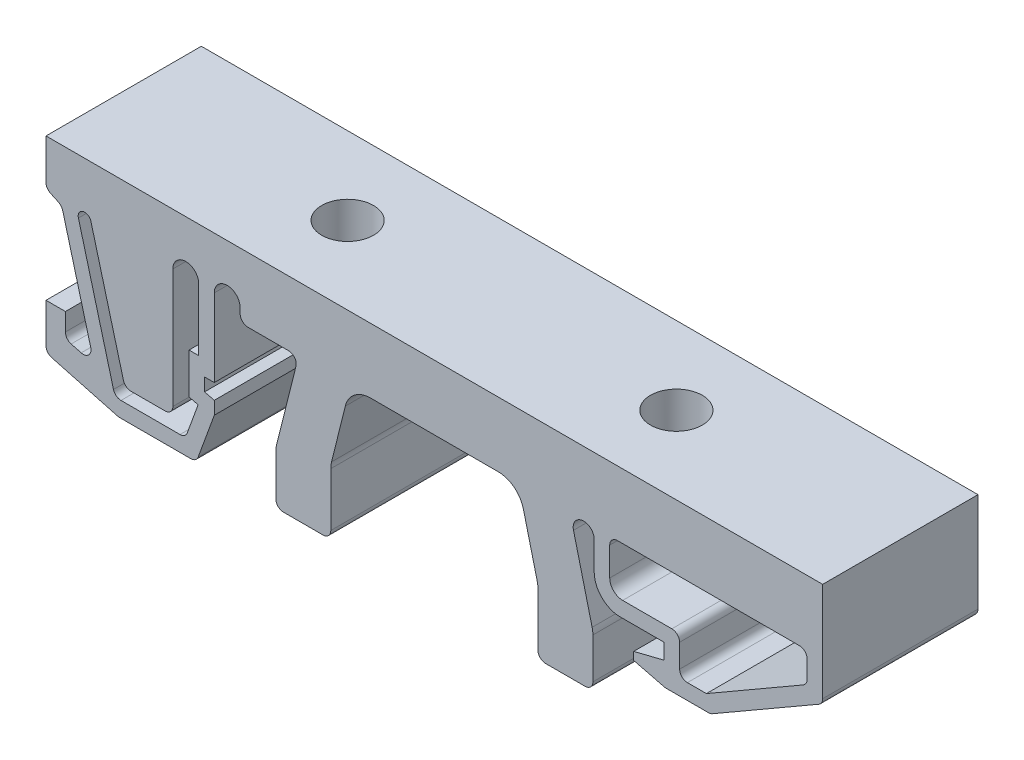
SolidWorks part; units mm, degrees
ref_plane "Front Plane" through (0, 0, 0) normal (0, 0, 1) x (1, 0, 0)
ref_plane "Top Plane" through (0, 0, 0) normal (0, 1, 0) x (1, 0, 0)
ref_plane "Right Plane" through (0, 0, 0) normal (1, 0, 0) x (0, 0, -1)
sketch "Sketch2" plane through (0, 0, 0) normal (0, 0, 1) x (1, 0, 0)
  line L0 (0, 22.5226) -> (0, -8.8845) construction
  line L1 (6.5, 11) -> (-6.5, 11)
  line L2 (-6.5, 11) -> (-8, 4.9838)
  line L3 (-8, 4.9838) -> (-8, 0)
  line L4 (-8, 0) -> (-12.25, 0)
  line L5 (-12.25, 0) -> (-12.25, 3.9811)
  line L6 (-12.25, 3.9811) -> (-10.5, 11)
  line L7 (-10.5, 11) -> (-15, 11)
  line L8 (-15, 11) -> (-15, 13)
  line L9 (-15, 13) -> (-17, 13)
  line L10 (-17, 13) -> (-17, 6)
  line L11 (-17, 6) -> (-17.75, 6)
  line L12 (-17.75, 6) -> (-17.75, 5)
  line L13 (-17.75, 5) -> (-17, 4.813)
  line L14 (-17, 4.813) -> (-17, 3.813)
  line L15 (-17, 3.813) -> (-18.3878, 0)
  line L16 (-18.3878, 0) -> (-24.3878, 0)
  line L17 (-24.3878, 0) -> (-30, 1.5038)
  line L18 (-30, 1.5038) -> (-30, 5.0038)
  line L19 (-30, 5.0038) -> (-28.5, 5.0038)
  line L20 (-28.5, 5.0038) -> (-28.5, 3.1724)
  line L21 (-28.5, 3.1724) -> (-26.2784, 2.5771)
  line L22 (-26.2784, 2.5771) -> (-28.7854, 11.9336)
  line L23 (-28.7854, 11.9336) -> (-30, 12.5)
  line L24 (-30, 12.5) -> (-30, 16)
  line L25 (-30, 16) -> (0, 16)
  line L30 (-8, 0) -> (0, 0) construction
  line L32 (10.5, 11) -> (12.35, 11)
  line L33 (12.25, 3.9811) -> (10.5, 11)
  line L34 (12.25, 0) -> (12.25, 3.9811)
  line L35 (8, 0) -> (12.25, 0)
  line L36 (8, 4.9838) -> (8, 0)
  line L37 (6.5, 11) -> (8, 4.9838)
  line L38 (12.35, 11) -> (12.35, 6)
  line L40 (12.35, 6) -> (17.75, 6)
  line L41 (17.75, 6) -> (17.75, 4.8)
  line L42 (17.75, 4.8) -> (15.4, 4.2141)
  line L43 (15.4, 4.2141) -> (15.4, 3.6083)
  line L44 (15.4, 3.6083) -> (17.8397, 3)
  line L45 (17.8397, 3) -> (21.3397, 3)
  line L46 (21.3397, 3) -> (30, 8)
  line L47 (30, 8) -> (30, 16)
  line L48 (30, 16) -> (0, 16)
  line L49 (-17.75, 6) -> (0, 6) construction
  line L50 (0, 6) -> (17.75, 6) construction
  line L54 (15.4, 3.9112) -> (22.918, 3.9112) construction
  line L56 (-8, 0) -> (8, 0) construction
  point P37 (0, 11)
  dimension "D1" = 5
  dimension "D2" = 16
  dimension "D3" = 104
  dimension "D4" = 16
  dimension "D5" = 13
  dimension "D6" = 24.5
  dimension "D7" = 4
  dimension "D8" = 2
  dimension "D9" = 2
  dimension "D10" = 4.5
  dimension "D11" = 35.5
  dimension "D12" = 7
  dimension "D13" = 1
  dimension "D14" = 1
  dimension "D15" = 20
  dimension "D16" = 6
  dimension "D17" = 15
  dimension "D18" = 1.5
  dimension "D19" = 3.5
  dimension "D20" = 2
  dimension "D21" = 60
  dimension "D22" = 60
  dimension "D23" = 50
  dimension "D24" = 3.5
  dimension "D25" = 2.3
  dimension "D26" = 60
  dimension "D27" = 8
  dimension "D28" = 15.4
  dimension "D29" = 3.5
  dimension "D30" = 1.2
  dimension "D31" = 5.4
  dimension "D32" = 3
extrude "Boss-Extrude1" add sketch "Sketch2" along normal mid plane 12
sketch "Sketch3" plane through (0, 0, 0) normal (0, 0, 1) x (1, 0, 0)
  line L0 (-27.6263, 12.2442) -> (-24.667, 1.2)
  line L1 (-24.667, 1.2) -> (-19.2281, 1.2)
  line L2 (-19.2281, 1.2) -> (-18.2498, 3.8879)
  line L3 (-18.2498, 3.8879) -> (-18.95, 4.0625)
  line L4 (-18.95, 4.0625) -> (-18.95, 7.2)
  line L5 (-18.95, 7.2) -> (-18.2, 7.2)
  line L6 (-18.2, 7.2) -> (-18.2, 13)
  line L7 (-18.2, 13) -> (-20.2, 13)
  line L8 (-20.2, 13) -> (-20.2, 2.2)
  line L9 (-20.2, 2.2) -> (-23.8997, 2.2)
  line L10 (-23.8997, 2.2) -> (-26.6604, 12.503)
  line L11 (-26.6604, 12.503) -> (-27.6263, 12.2442)
  line L12 (13.55, 11) -> (13.55, 7.2)
  line L13 (13.55, 7.2) -> (18.95, 7.2)
  line L14 (18.95, 7.2) -> (18.95, 4.2)
  line L15 (18.95, 4.2) -> (21.0182, 4.2)
  line L16 (21.0182, 4.2) -> (28.8, 8.6928)
  line L17 (28.8, 8.6928) -> (28.8, 11)
  line L18 (28.8, 11) -> (13.55, 11)
  line L19 (-28.7854, 11.9336) -> (-26.2784, 2.5771) construction
  line L20 (-18.3878, 0) -> (-17, 3.813) construction
  line L21 (-24.3878, 0) -> (-18.3878, 0) construction
  line L22 (-17.75, 5) -> (-17.75, 6) construction
  line L23 (-17, 6) -> (-17, 13) construction
  line L26 (-17, 4.813) -> (-17.75, 5) construction
  line L27 (-17.75, 6) -> (-17, 6) construction
  line L28 (-17, 13) -> (-15, 13) construction
  line L29 (12.35, 11) -> (12.35, 6) construction
  line L30 (12.35, 6) -> (17.75, 6) construction
  line L31 (17.75, 6) -> (17.75, 4.8) construction
  line L32 (30, 8) -> (30, 16) construction
  line L33 (21.3397, 3) -> (30, 8) construction
  line L34 (17.8397, 3) -> (21.3397, 3) construction
  line L35 (10.5, 11) -> (12.35, 11) construction
  dimension "D1" = 1.2
  dimension "D2" = 1.2
  dimension "D3" = 1.2
  dimension "D4" = 1.2
  dimension "D5" = 1.2
  dimension "D6" = 2
  dimension "D7" = 1
  dimension "D8" = 1.2
  dimension "D9" = 1.2
  dimension "D10" = 1.2
  dimension "D11" = 1.2
  dimension "D12" = 1.2
  dimension "D13" = 1.2
  dimension "D14" = 1.2
  dimension "D15" = 1.2
  dimension "D16" = 1
extrude "Cut-Extrude1" cut sketch "Sketch3" against normal through all both and the other way through all
fillet "Fillet1" radius 2 1 edges at (12.35, 6, 0)
fillet "Fillet2" radius 1 1 edges at (13.55, 7.2, 0)
fillet "Fillet3" 2 edges at (10.5, 11, 0) (12.35, 11, 0) type full round first side face at (11.375, 7.4906, 0) second side face at (12.35, 9.5, 0) middle face at (11.425, 11, 0)
fillet "Fillet4" radius 2 6 edges at (-12.25, 3.9811, 0) (12.25, 3.9811, 0) (8, 4.9838, 0) (-8, 4.9838, 0) (-6.5, 11, 0) (6.5, 11, 0)
fillet "Fillet5" 2 edges at (-20.2, 13, 0) (-18.2, 13, 0) type full round first side face at (-20.2, 7.6, 0) second side face at (-18.2, 10.1, 0) middle face at (-19.2, 13, 0)
fillet "Fillet6" 2 edges at (-17, 13, 0) (-15, 13, 0) type full round first side face at (-17, 9.5, 0) second side face at (-15, 12, 0) middle face at (-16, 13, 0)
fillet "Fillet7" 2 edges at (-27.6263, 12.2442, 0) (-26.6604, 12.503, 0) type full round first side face at (-26.1467, 6.7221, 0) second side face at (-25.2801, 7.3515, 0) middle face at (-27.1434, 12.3736, 0)
fillet "Fillet8" radius 0.6 25 edges at (-10.5, 11, 0) (-12.25, 0, 0) (-8, 0, 0) (8, 0, 0) (12.25, 0, 0) (17.8397, 3, 0) (28.8, 8.6928, 0) (28.8, 11, 0) (13.55, 11, 0) (18.95, 7.2, 0) (18.95, 4.2, 0) (21.3397, 3, 0) (30, 8, 0) (-23.8997, 2.2, 0) (-20.2, 2.2, 0) (-30, 1.5038, 0) (-28.5, 3.1724, 0) (-26.2784, 2.5771, 0) (-24.667, 1.2, 0) (-19.2281, 1.2, 0) (-24.3878, 0, 0) (-18.3878, 0, 0) (-15, 11, 0) (-30, 12.5, 0) (-28.7854, 11.9336, 0)
sketch "Sketch4" plane through (0, 16, 0) normal (0, 1, 0) x (1, 0, 0)
  line L0 (0, 0) -> (-12.7, 0) construction
  line L3 (0, 0) -> (0, -6) construction
  line L4 (30, -6) -> (-30, -6) construction
  circle A0 centre (-12.7, 0) radius 2
  circle A1 centre (12.7, 0) radius 2
  dimension "D1" = 4
  dimension "D2" = 25.4
extrude "Cut-Extrude2" cut sketch "Sketch4" against normal blind 8.5
